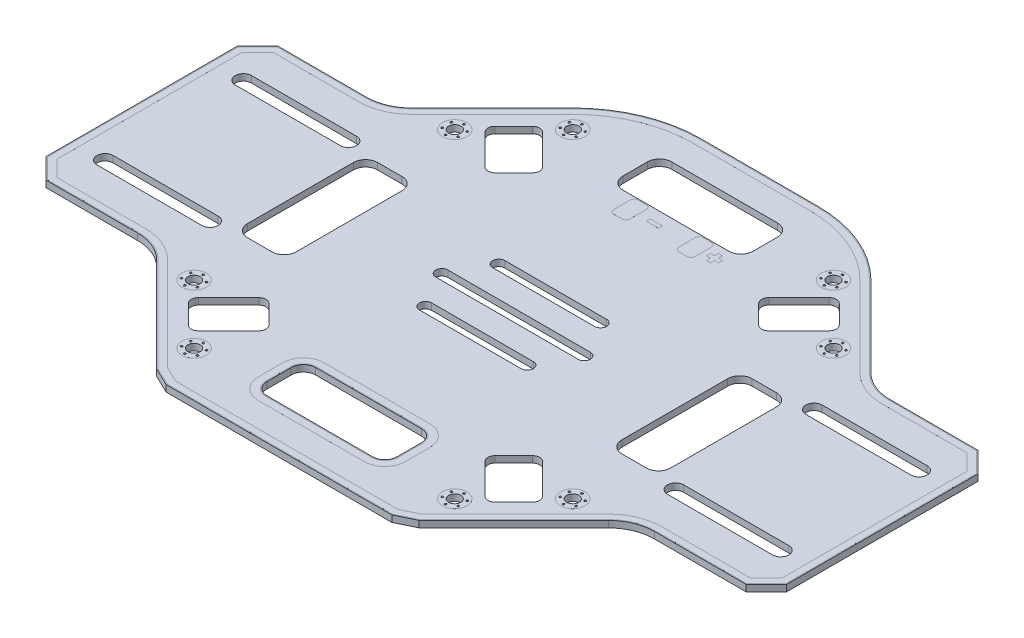
SolidWorks part; units mm, degrees
material "PLA"
ref_plane "Front Plane" through (0, 0, 0) normal (0, 0, 1) x (1, 0, 0)
ref_plane "Top Plane" through (0, 0, 0) normal (0, 1, 0) x (1, 0, 0)
ref_plane "Right Plane" through (0, 0, 0) normal (1, 0, 0) x (0, 0, -1)
sketch "Sketch1" plane through (0, 0, 0) normal (0, 1, 0) x (1, 0, 0)
  line L0 (0, 60.3186) -> (0, -57.6814) construction
  line L1 (-27.75, -57.6814) -> (27.75, -57.6814)
  line L2 (-13, -47.6814) -> (13, -47.6814)
  line L3 (-16, -38.6814) -> (-16, -44.6814)
  line L4 (16, -38.6814) -> (16, -44.6814)
  line L5 (-16, -41.6814) -> (16, -41.6814) construction
  line L6 (-13, -35.6814) -> (13, -35.6814)
  line L7 (-27.75, -57.6814) -> (-32.25, -55.502)
  line L8 (27.75, -57.6814) -> (32.25, -55.502)
  line L9 (-32.25, -55.502) -> (32.25, -55.502) construction
  line L10 (32.25, -55.502) -> (55.502, -32.25)
  line L11 (-32.25, -55.502) -> (-55.502, -32.25)
  line L12 (-43.876, 43.876) -> (43.876, -43.876) construction
  line L13 (-43.876, -43.876) -> (43.876, 43.876) construction
  line L14 (37.6888, -42.285) -> (42.285, -37.6888)
  line L15 (27.7893, -34.8604) -> (35.2139, -42.285)
  line L16 (34.8604, -27.7893) -> (42.285, -35.2139)
  line L17 (31.5016, -38.5727) -> (38.5727, -31.5016) construction
  line L18 (27.7893, -32.3855) -> (32.3855, -27.7893)
  line L19 (-38.5727, -31.5016) -> (-31.5016, -38.5727) construction
  line L20 (-35.2139, -42.285) -> (-27.7893, -34.8604)
  line L21 (-42.285, -35.2139) -> (-34.8604, -27.7893)
  line L22 (-32.3855, -27.7893) -> (-27.7893, -32.3855)
  line L23 (-42.285, -37.6888) -> (-37.6888, -42.285)
  line L24 (-63.5, -28.9371) -> (63.5, -28.9371) construction
  line L25 (63.5, -28.9371) -> (86, -28.9371)
  line L26 (-63.5, -28.9371) -> (-86, -28.9371)
  line L27 (-91, -23.9371) -> (-91, 23.0629)
  line L28 (91, -23.9371) -> (91, 23.0629)
  line L29 (-86, -28.9371) -> (-86, 28.0629) construction
  line L30 (86, -28.9371) -> (86, 28.0629) construction
  line L31 (-91, -0.4371) -> (-86, -0.4371) construction
  line L32 (86, -0.4371) -> (91, -0.4371) construction
  line L33 (86, -28.9371) -> (91, -23.9371)
  line L34 (-91, -23.9371) -> (-86, -28.9371)
  line L35 (91, 23.0629) -> (86, 28.0629)
  line L36 (-91, 23.0629) -> (-86, 28.0629)
  line L37 (-56.4271, 31.3248) -> (-36.6281, 51.1238)
  line L38 (36.6281, 51.1238) -> (56.4271, 31.3248)
  line L39 (-35.2139, 42.285) -> (-27.7893, 34.8604)
  line L40 (-36.6281, 51.1238) -> (-27.7893, 42.285) construction
  line L41 (-27.7893, 42.285) -> (-31.5016, 38.5727) construction
  line L42 (-42.285, 35.2139) -> (-34.8604, 27.7893)
  line L43 (-31.5016, 38.5727) -> (-38.5727, 31.5016) construction
  line L44 (-42.285, 37.6888) -> (-37.6888, 42.285)
  line L45 (-32.3855, 27.7893) -> (-27.7893, 32.3855)
  line L46 (-86, 28.0629) -> (-64.3021, 28.0629)
  line L47 (86, 28.0629) -> (64.3021, 28.0629)
  line L48 (37.6888, 42.285) -> (42.285, 37.6888)
  line L49 (27.7893, 32.3855) -> (32.3855, 27.7893)
  line L50 (27.7893, 34.8604) -> (35.2139, 42.285)
  line L51 (34.8604, 27.7893) -> (42.285, 35.2139)
  line L52 (31.5016, 38.5727) -> (38.5727, 31.5016) construction
  line L53 (31.5016, 38.5727) -> (27.7893, 42.285) construction
  line L54 (27.7893, 42.285) -> (36.6281, 51.1238) construction
  line L55 (-14.43, 60.3186) -> (14.43, 60.3186)
  line L56 (-13, 51.8186) -> (13, 51.8186)
  line L57 (-13, 39.8186) -> (13, 39.8186)
  line L58 (16, 48.8186) -> (16, 42.8186)
  line L59 (-16, 48.8186) -> (-16, 42.8186)
  line L60 (-12.5, -10.6814) -> (12.5, -10.6814)
  line L61 (-12.5, -7.6814) -> (12.5, -7.6814)
  line L62 (-17.5, -1.6814) -> (17.5, -1.6814)
  line L63 (-17.5, 1.3186) -> (17.5, 1.3186)
  line L64 (-12.5, 7.3186) -> (12.5, 7.3186)
  line L65 (-12.5, 10.3186) -> (12.5, 10.3186)
  line L66 (-52, 12.5629) -> (-52, -13.4371)
  line L67 (-86, -0.4371) -> (-52, -0.4371) construction
  line L68 (-40, 12.5629) -> (-40, -13.4371)
  line L69 (52, 12.5629) -> (52, -13.4371)
  line L70 (-49, 15.5629) -> (-43, 15.5629)
  line L71 (-49, -16.4371) -> (-43, -16.4371)
  line L72 (86, -0.4371) -> (52, -0.4371) construction
  line L73 (40, 12.5629) -> (40, -13.4371)
  line L74 (43, 15.5629) -> (49, 15.5629)
  line L75 (43, -16.4371) -> (49, -16.4371)
  line L76 (-83, 18.5629) -> (-57.2, 18.5629)
  line L77 (-83, 14.5629) -> (-57.2, 14.5629)
  line L78 (-83, -15.4371) -> (-57.2, -15.4371)
  line L79 (-83, -19.4371) -> (-57.2, -19.4371)
  line L80 (57.2, -15.4371) -> (83, -15.4371)
  line L81 (57.2, -19.4371) -> (83, -19.4371)
  line L82 (57.2, 18.5629) -> (83, 18.5629)
  line L83 (57.2, 14.5629) -> (83, 14.5629)
  line L84 (-46.5276, 32.0319) -> (-32.0319, 46.5276) construction
  line L85 (32.0319, -46.5276) -> (46.5276, -32.0319) construction
  arc A0 (-16, -44.6814) -> (-13, -47.6814) centre (-13, -44.6814) ccw
  arc A1 (-13, -35.6814) -> (-16, -38.6814) centre (-13, -38.6814) ccw
  arc A2 (16, -38.6814) -> (13, -35.6814) centre (13, -38.6814) ccw
  arc A3 (13, -47.6814) -> (16, -44.6814) centre (13, -44.6814) ccw
  arc A4 (27.7893, -32.3855) -> (27.7893, -34.8604) centre (29.0267, -33.6229) ccw
  arc A5 (34.8604, -27.7893) -> (32.3855, -27.7893) centre (33.6229, -29.0267) ccw
  arc A6 (35.2139, -42.285) -> (37.6888, -42.285) centre (36.4514, -41.0475) ccw
  arc A7 (42.285, -37.6888) -> (42.285, -35.2139) centre (41.0475, -36.4514) ccw
  arc A8 (-37.6888, -42.285) -> (-35.2139, -42.285) centre (-36.4514, -41.0475) ccw
  arc A9 (-42.285, -35.2139) -> (-42.285, -37.6888) centre (-41.0475, -36.4514) ccw
  arc A10 (-32.3855, -27.7893) -> (-34.8604, -27.7893) centre (-33.6229, -29.0267) ccw
  arc A11 (-27.7893, -34.8604) -> (-27.7893, -32.3855) centre (-29.0267, -33.6229) ccw
  arc A12 (-55.502, -32.25) -> (-63.5, -28.9371) centre (-63.5, -40.248) ccw
  arc A13 (63.5, -28.9371) -> (55.502, -32.25) centre (63.5, -40.248) ccw
  arc A14 (-42.285, 37.6888) -> (-42.285, 35.2139) centre (-41.0475, 36.4514) ccw
  arc A15 (-35.2139, 42.285) -> (-37.6888, 42.285) centre (-36.4514, 41.0475) ccw
  arc A16 (-27.7893, 32.3855) -> (-27.7893, 34.8604) centre (-29.0267, 33.6229) ccw
  arc A17 (-34.8604, 27.7893) -> (-32.3855, 27.7893) centre (-33.6229, 29.0267) ccw
  arc A18 (-64.3021, 28.0629) -> (-56.4271, 31.3248) centre (-64.3021, 39.1998) ccw
  arc A19 (56.4271, 31.3248) -> (64.3021, 28.0629) centre (64.3021, 39.1998) ccw
  arc A20 (27.7893, 34.8604) -> (27.7893, 32.3855) centre (29.0267, 33.6229) ccw
  arc A21 (37.6888, 42.285) -> (35.2139, 42.285) centre (36.4514, 41.0475) ccw
  arc A22 (42.285, 35.2139) -> (42.285, 37.6888) centre (41.0475, 36.4514) ccw
  arc A23 (32.3855, 27.7893) -> (34.8604, 27.7893) centre (33.6229, 29.0267) ccw
  arc A24 (-14.43, 60.3186) -> (-36.6281, 51.1238) centre (-14.43, 28.9257) ccw
  arc A25 (13, 39.8186) -> (16, 42.8186) centre (13, 42.8186) ccw
  arc A26 (36.6281, 51.1238) -> (14.43, 60.3186) centre (14.43, 28.9257) ccw
  arc A27 (16, 48.8186) -> (13, 51.8186) centre (13, 48.8186) ccw
  arc A28 (-16, 42.8186) -> (-13, 39.8186) centre (-13, 42.8186) ccw
  arc A29 (-13, 51.8186) -> (-16, 48.8186) centre (-13, 48.8186) ccw
  arc A30 (-12.5, -7.6814) -> (-12.5, -10.6814) centre (-12.5, -9.1814) ccw
  arc A31 (12.5, -10.6814) -> (12.5, -7.6814) centre (12.5, -9.1814) ccw
  arc A32 (-17.5, 1.3186) -> (-17.5, -1.6814) centre (-17.5, -0.1814) ccw
  arc A33 (17.5, -1.6814) -> (17.5, 1.3186) centre (17.5, -0.1814) ccw
  arc A34 (-12.5, 10.3186) -> (-12.5, 7.3186) centre (-12.5, 8.8186) ccw
  arc A35 (12.5, 7.3186) -> (12.5, 10.3186) centre (12.5, 8.8186) ccw
  arc A36 (-49, 15.5629) -> (-52, 12.5629) centre (-49, 12.5629) ccw
  arc A37 (-40, 12.5629) -> (-43, 15.5629) centre (-43, 12.5629) ccw
  arc A38 (-52, -13.4371) -> (-49, -16.4371) centre (-49, -13.4371) ccw
  arc A39 (-43, -16.4371) -> (-40, -13.4371) centre (-43, -13.4371) ccw
  arc A40 (43, 15.5629) -> (40, 12.5629) centre (43, 12.5629) ccw
  arc A41 (52, 12.5629) -> (49, 15.5629) centre (49, 12.5629) ccw
  arc A42 (40, -13.4371) -> (43, -16.4371) centre (43, -13.4371) ccw
  arc A43 (49, -16.4371) -> (52, -13.4371) centre (49, -13.4371) ccw
  arc A44 (-57.2, 14.5629) -> (-57.2, 18.5629) centre (-57.2, 16.5629) ccw
  arc A45 (-83, 18.5629) -> (-83, 14.5629) centre (-83, 16.5629) ccw
  arc A46 (-83, -15.4371) -> (-83, -19.4371) centre (-83, -17.4371) ccw
  arc A47 (-57.2, -19.4371) -> (-57.2, -15.4371) centre (-57.2, -17.4371) ccw
  arc A48 (57.2, -15.4371) -> (57.2, -19.4371) centre (57.2, -17.4371) ccw
  arc A49 (83, -19.4371) -> (83, -15.4371) centre (83, -17.4371) ccw
  arc A50 (57.2, 18.5629) -> (57.2, 14.5629) centre (57.2, 16.5629) ccw
  arc A51 (83, 14.5629) -> (83, 18.5629) centre (83, 16.5629) ccw
  circle A52 centre (-32.0319, 46.5276) radius 1.5
  circle A53 centre (-46.5276, 32.0319) radius 1.5
  circle A54 centre (32.0319, -46.5276) radius 1.5
  circle A55 centre (46.5276, -32.0319) radius 1.5
  circle A56 centre (-46.5276, -32.0319) radius 1.5
  circle A57 centre (-32.0319, -46.5276) radius 1.5
  circle A58 centre (32.0319, 46.5276) radius 1.5
  circle A59 centre (46.5276, 32.0319) radius 1.5
  point P4 (-35.0371, 35.0371)
  point P5 (0, -47.6814)
  point P14 (0, -41.6814)
  point P15 (0, -35.6814)
  point P19 (0, -55.502)
  point P29 (0, 0)
  point P30 (39.9869, -39.9869)
  point P32 (0, 0)
  point P42 (30.0874, -30.0874)
  point P43 (35.0371, -35.0371)
  point P50 (-35.0371, -35.0371)
  point P53 (-38.5727, -31.5016)
  point P62 (-39.9869, -39.9869)
  point P63 (-30.0874, -30.0874)
  point P70 (0, -28.9371)
  point P99 (-39.9869, 39.9869)
  point P102 (-30.0874, 30.0874)
  point P119 (35.0371, 35.0371)
  point P122 (39.9869, 39.9869)
  point P123 (30.0874, 30.0874)
  point P135 (0, 51.8186)
  point P138 (0, 39.8186)
  point P147 (0, -10.6814)
  point P151 (-14, -9.1814)
  point P153 (14, -9.1814)
  point P156 (0, -1.6814)
  point P158 (-19, -0.1814)
  point P162 (19, -0.1814)
  point P167 (0, 7.3186)
  point P203 (-85, 16.5629)
  point P205 (-55.2, 16.5629)
  point P217 (85, -17.4371)
  point P229 (-39.2798, 39.2798)
  point P232 (39.2798, -39.2798)
  dimension "D5" = 12
  dimension "D6" = 55.5
  dimension "D14" = 14
  dimension "D15" = 127
  dimension "D16" = 22.5
  dimension "D23" = 8.5
  dimension "D24" = 25
  dimension "D25" = 3
  dimension "D28" = 3
  dimension "D31" = 39
  dimension "D32" = 9.5
  dimension "D34" = 29.8
  dimension "D38" = 6
  dimension "D39" = 3
  dimension "D1" = 118
  dimension "D2" = 10
  dimension "D3" = 32
  dimension "D4" = 6
  dimension "D7" = 64.5
  dimension "D8" = 5
  dimension "D9" = 124.1
  dimension "D10" = 45
  dimension "D11" = 5.5
  dimension "D12" = 6.5
  dimension "D13" = 10
  dimension "D17" = 22.5
  dimension "D18" = 5
  dimension "D19" = 45
  dimension "D20" = 47
  dimension "D21" = 28
  dimension "D22" = 5.25
  dimension "D26" = 28
  dimension "D27" = 6
  dimension "D29" = 38
  dimension "D30" = 6
  dimension "D33" = 4
  dimension "D35" = 6
  dimension "D36" = 9.5
  dimension "D37" = 4
  dimension "D40" = 6.5
  dimension "D41" = 6.5
extrude "Boss-Extrude1" add sketch "Sketch1" along normal blind 0.8 and the other way blind 0.8
sketch "Sketch2" plane through (0, 0.8, 0) normal (0, 1, 0) x (1, 0, 0)
  line L0 (-27.6926, -57.4314) -> (27.6926, -57.4314)
  line L1 (-27.75, -57.6814) -> (27.75, -57.6814) construction
  line L2 (-27.6926, -57.4314) -> (-32.1031, -55.2953)
  line L3 (-32.25, -55.502) -> (-27.75, -57.6814) construction
  line L4 (27.6926, -57.4314) -> (32.1031, -55.2953)
  line L5 (27.75, -57.6814) -> (32.25, -55.502) construction
  line L6 (0, -57.6814) -> (0, -57.4314) construction
  line L7 (-32.1031, -55.2953) -> (-55.3252, -32.0732)
  line L8 (-55.502, -32.25) -> (-32.25, -55.502) construction
  line L9 (32.1031, -55.2953) -> (55.3252, -32.0732)
  line L10 (32.25, -55.502) -> (55.502, -32.25) construction
  line L11 (-85.8964, -28.6871) -> (-63.5, -28.6871)
  line L12 (-85.8964, -28.6871) -> (-90.75, -23.8335)
  line L13 (-91, -23.9371) -> (-86, -28.9371) construction
  line L14 (-86, -28.9371) -> (-63.5, -28.9371) construction
  line L15 (63.5, -28.6871) -> (85.8964, -28.6871)
  line L16 (85.8964, -28.6871) -> (90.75, -23.8335)
  line L17 (-90.75, -23.8335) -> (-90.75, 22.9593)
  line L18 (-91, 23.0629) -> (-91, -23.9371) construction
  line L19 (-90.75, 22.9593) -> (-85.8964, 27.8129)
  line L20 (-85.8964, 27.8129) -> (-64.3021, 27.8129)
  line L21 (-64.3021, 28.0629) -> (-86, 28.0629) construction
  line L22 (-56.2503, 31.1481) -> (-36.4514, 50.947)
  line L23 (-36.6281, 51.1238) -> (-56.4271, 31.3248) construction
  line L24 (-14.43, 60.0686) -> (14.43, 60.0686)
  line L25 (14.43, 60.3186) -> (-14.43, 60.3186) construction
  line L26 (56.2503, 31.1481) -> (36.4514, 50.947)
  line L27 (56.4271, 31.3248) -> (36.6281, 51.1238) construction
  line L28 (64.3021, 27.8129) -> (85.8964, 27.8129)
  line L29 (86, 28.0629) -> (64.3021, 28.0629) construction
  line L30 (85.8964, 27.8129) -> (90.75, 22.9593)
  line L31 (91, 23.0629) -> (86, 28.0629) construction
  line L32 (90.75, 22.9593) -> (90.75, -23.8335)
  line L33 (-55.0836, 29.9813) -> (-35.2846, 49.7803)
  line L34 (-14.43, 58.4186) -> (14.43, 58.4186)
  line L35 (55.0836, 29.9813) -> (35.2846, 49.7803)
  line L36 (64.3021, 26.1629) -> (85.213, 26.1629)
  line L37 (85.213, 26.1629) -> (89.1, 22.2759)
  line L38 (89.1, 22.2759) -> (89.1, -23.1501)
  line L39 (85.213, -27.0371) -> (89.1, -23.1501)
  line L40 (63.5, -27.0371) -> (85.213, -27.0371)
  line L41 (31.1332, -53.9317) -> (54.1584, -30.9065)
  line L42 (27.3141, -55.7814) -> (31.1332, -53.9317)
  line L43 (-27.3141, -55.7814) -> (27.3141, -55.7814)
  line L44 (-27.3141, -55.7814) -> (-31.1332, -53.9317)
  line L45 (-31.1332, -53.9317) -> (-54.1584, -30.9065)
  line L46 (-85.213, -27.0371) -> (-63.5, -27.0371)
  line L47 (-85.213, -27.0371) -> (-89.1, -23.1501)
  line L48 (-89.1, -23.1501) -> (-89.1, 22.2759)
  line L49 (-89.1, 22.2759) -> (-85.213, 26.1629)
  line L50 (-85.213, 26.1629) -> (-64.3021, 26.1629)
  line L51 (-13, -35.4314) -> (13, -35.4314)
  line L52 (-16.25, -38.6814) -> (-16.25, -44.6814)
  line L53 (-13, -47.9314) -> (13, -47.9314)
  line L54 (16.25, -44.6814) -> (16.25, -38.6814)
  line L55 (16, -44.6814) -> (16, -38.6814) construction
  line L56 (13, -35.6814) -> (-13, -35.6814) construction
  line L57 (-16, -38.6814) -> (-16, -44.6814) construction
  line L58 (-13, -47.6814) -> (13, -47.6814) construction
  line L59 (-13, -33.6314) -> (13, -33.6314)
  line L60 (18.05, -44.6814) -> (18.05, -38.6814)
  line L61 (-13, -49.7314) -> (13, -49.7314)
  line L62 (-18.05, -38.6814) -> (-18.05, -44.6814)
  line L63 (32.0319, -43.5276) -> (32.0319, -44.2776) construction
  line L64 (-32.0319, -44.2776) -> (-33.9805, -45.4026) construction
  line L65 (-33.9805, -45.4026) -> (-33.9805, -47.6526) construction
  line L66 (-33.9805, -47.6526) -> (-32.0319, -48.7776) construction
  line L67 (-32.0319, -48.7776) -> (-30.0834, -47.6526) construction
  line L68 (-30.0834, -47.6526) -> (-30.0834, -45.4026) construction
  line L69 (-30.0834, -45.4026) -> (-32.0319, -44.2776) construction
  line L70 (-46.5276, -29.7819) -> (-48.4762, -30.9069) construction
  line L71 (-48.4762, -30.9069) -> (-48.4762, -33.1569) construction
  line L72 (-48.4762, -33.1569) -> (-46.5276, -34.2819) construction
  line L73 (-46.5276, -34.2819) -> (-44.5791, -33.1569) construction
  line L74 (-44.5791, -33.1569) -> (-44.5791, -30.9069) construction
  line L75 (-44.5791, -30.9069) -> (-46.5276, -29.7819) construction
  line L76 (-46.5276, 34.2819) -> (-48.4762, 33.1569) construction
  line L77 (-48.4762, 33.1569) -> (-48.4762, 30.9069) construction
  line L78 (-48.4762, 30.9069) -> (-46.5276, 29.7819) construction
  line L79 (-46.5276, 29.7819) -> (-44.5791, 30.9069) construction
  line L80 (-44.5791, 30.9069) -> (-44.5791, 33.1569) construction
  line L81 (-44.5791, 33.1569) -> (-46.5276, 34.2819) construction
  line L82 (-32.0319, 48.7776) -> (-33.9805, 47.6526) construction
  line L83 (-33.9805, 47.6526) -> (-33.9805, 45.4026) construction
  line L84 (-33.9805, 45.4026) -> (-32.0319, 44.2776) construction
  line L85 (-32.0319, 44.2776) -> (-30.0834, 45.4026) construction
  line L86 (-30.0834, 45.4026) -> (-30.0834, 47.6526) construction
  line L87 (-30.0834, 47.6526) -> (-32.0319, 48.7776) construction
  line L88 (32.0319, 48.7776) -> (30.0834, 47.6526) construction
  line L89 (30.0834, 47.6526) -> (30.0834, 45.4026) construction
  line L90 (30.0834, 45.4026) -> (32.0319, 44.2776) construction
  line L91 (32.0319, 44.2776) -> (33.9805, 45.4026) construction
  line L92 (33.9805, 45.4026) -> (33.9805, 47.6526) construction
  line L93 (33.9805, 47.6526) -> (32.0319, 48.7776) construction
  line L94 (46.5276, 34.2819) -> (44.5791, 33.1569) construction
  line L95 (44.5791, 33.1569) -> (44.5791, 30.9069) construction
  line L96 (44.5791, 30.9069) -> (46.5276, 29.7819) construction
  line L97 (46.5276, 29.7819) -> (48.4762, 30.9069) construction
  line L98 (48.4762, 30.9069) -> (48.4762, 33.1569) construction
  line L99 (48.4762, 33.1569) -> (46.5276, 34.2819) construction
  line L100 (46.5276, -29.7819) -> (44.5791, -30.9069) construction
  line L101 (44.5791, -30.9069) -> (44.5791, -33.1569) construction
  line L102 (44.5791, -33.1569) -> (46.5276, -34.2819) construction
  line L103 (46.5276, -34.2819) -> (48.4762, -33.1569) construction
  line L104 (48.4762, -33.1569) -> (48.4762, -30.9069) construction
  line L105 (48.4762, -30.9069) -> (46.5276, -29.7819) construction
  line L106 (32.0319, -44.2776) -> (30.0834, -45.4026) construction
  line L107 (30.0834, -45.4026) -> (30.0834, -47.6526) construction
  line L108 (30.0834, -47.6526) -> (32.0319, -48.7776) construction
  line L109 (32.0319, -48.7776) -> (33.9805, -47.6526) construction
  line L110 (33.9805, -47.6526) -> (33.9805, -45.4026) construction
  line L111 (33.9805, -45.4026) -> (32.0319, -44.2776) construction
  line L112 (32.0319, -44.2776) -> (32.0319, -45.0276) construction
  arc A0 (-55.3252, -32.0732) -> (-63.5, -28.6871) centre (-63.5, -40.248) ccw
  arc A1 (-55.502, -32.25) -> (-63.5, -28.9371) centre (-63.5, -40.248) ccw construction
  arc A2 (63.5, -28.6871) -> (55.3252, -32.0732) centre (63.5, -40.248) ccw
  arc A3 (63.5, -28.9371) -> (55.502, -32.25) centre (63.5, -40.248) ccw construction
  arc A4 (-64.3021, 27.8129) -> (-56.2503, 31.1481) centre (-64.3021, 39.1998) ccw
  arc A5 (-64.3021, 28.0629) -> (-56.4271, 31.3248) centre (-64.3021, 39.1998) ccw construction
  arc A6 (-14.43, 60.0686) -> (-36.4514, 50.947) centre (-14.43, 28.9257) ccw
  arc A7 (-14.43, 60.3186) -> (-36.6281, 51.1238) centre (-14.43, 28.9257) ccw construction
  arc A8 (36.4514, 50.947) -> (14.43, 60.0686) centre (14.43, 28.9257) ccw
  arc A9 (36.6281, 51.1238) -> (14.43, 60.3186) centre (14.43, 28.9257) ccw construction
  arc A10 (56.2503, 31.1481) -> (64.3021, 27.8129) centre (64.3021, 39.1998) ccw
  arc A11 (56.4271, 31.3248) -> (64.3021, 28.0629) centre (64.3021, 39.1998) ccw construction
  arc A12 (-14.43, 58.4186) -> (-35.2846, 49.7803) centre (-14.43, 28.9257) ccw
  arc A13 (35.2846, 49.7803) -> (14.43, 58.4186) centre (14.43, 28.9257) ccw
  arc A14 (55.0836, 29.9813) -> (64.3021, 26.1629) centre (64.3021, 39.1998) ccw
  arc A15 (63.5, -27.0371) -> (54.1584, -30.9065) centre (63.5, -40.248) ccw
  arc A16 (-54.1584, -30.9065) -> (-63.5, -27.0371) centre (-63.5, -40.248) ccw
  arc A17 (-64.3021, 26.1629) -> (-55.0836, 29.9813) centre (-64.3021, 39.1998) ccw
  arc A18 (-13, -35.4314) -> (-16.25, -38.6814) centre (-13, -38.6814) ccw
  arc A19 (16.25, -38.6814) -> (13, -35.4314) centre (13, -38.6814) ccw
  arc A20 (-16.25, -44.6814) -> (-13, -47.9314) centre (-13, -44.6814) ccw
  arc A21 (13, -47.9314) -> (16.25, -44.6814) centre (13, -44.6814) ccw
  arc A22 (-13, -35.6814) -> (-16, -38.6814) centre (-13, -38.6814) ccw construction
  arc A23 (-16, -44.6814) -> (-13, -47.6814) centre (-13, -44.6814) ccw construction
  arc A24 (16, -38.6814) -> (13, -35.6814) centre (13, -38.6814) ccw construction
  arc A25 (13, -47.6814) -> (16, -44.6814) centre (13, -44.6814) ccw construction
  arc A26 (18.05, -38.6814) -> (13, -33.6314) centre (13, -38.6814) ccw
  arc A27 (13, -49.7314) -> (18.05, -44.6814) centre (13, -44.6814) ccw
  arc A28 (-18.05, -44.6814) -> (-13, -49.7314) centre (-13, -44.6814) ccw
  arc A29 (-13, -33.6314) -> (-18.05, -38.6814) centre (-13, -38.6814) ccw
  circle A30 centre (-32.0319, -46.5276) radius 1.5
  circle A31 centre (-46.5276, -32.0319) radius 1.5
  circle A32 centre (-46.5276, 32.0319) radius 1.5
  circle A33 centre (-32.0319, 46.5276) radius 1.5
  circle A34 centre (32.0319, 46.5276) radius 1.5
  circle A35 centre (46.5276, 32.0319) radius 1.5
  circle A36 centre (46.5276, -32.0319) radius 1.5
  circle A37 centre (32.0319, -46.5276) radius 1.5
  circle A38 centre (-32.0319, -46.5276) radius 1.5 construction
  circle A39 centre (-46.5276, -32.0319) radius 1.5 construction
  circle A40 centre (-46.5276, 32.0319) radius 1.5 construction
  circle A41 centre (-32.0319, 46.5276) radius 1.5 construction
  circle A42 centre (32.0319, 46.5276) radius 1.5 construction
  circle A43 centre (46.5276, 32.0319) radius 1.5 construction
  circle A44 centre (46.5276, -32.0319) radius 1.5 construction
  circle A45 centre (32.0319, -46.5276) radius 1.5 construction
  circle A46 centre (-32.0319, -46.5276) radius 3
  circle A47 centre (-46.5276, -32.0319) radius 3
  circle A48 centre (-46.5276, 32.0319) radius 3
  circle A49 centre (-32.0319, 46.5276) radius 3
  circle A50 centre (32.0319, 46.5276) radius 3
  circle A51 centre (46.5276, 32.0319) radius 3
  circle A52 centre (46.5276, -32.0319) radius 3
  circle A53 centre (32.0319, -46.5276) radius 3
  circle A54 centre (-32.0319, -46.5276) radius 1.9486 construction
  circle A55 centre (-46.5276, -32.0319) radius 1.9486 construction
  circle A56 centre (-46.5276, 32.0319) radius 1.9486 construction
  circle A57 centre (-32.0319, 46.5276) radius 1.9486 construction
  circle A58 centre (32.0319, 46.5276) radius 1.9486 construction
  circle A59 centre (46.5276, 32.0319) radius 1.9486 construction
  circle A60 centre (46.5276, -32.0319) radius 1.9486 construction
  circle A61 centre (32.0319, -46.5276) radius 1.9486 construction
  circle A62 centre (32.0319, -44.2776) radius 0.25
  circle A63 centre (33.9805, -45.4026) radius 0.25
  circle A64 centre (33.9805, -47.6526) radius 0.25
  circle A65 centre (32.0319, -48.7776) radius 0.25
  circle A66 centre (30.0834, -47.6526) radius 0.25
  circle A67 centre (30.0834, -45.4026) radius 0.25
  circle A68 centre (46.5276, -34.2819) radius 0.25
  circle A69 centre (48.4762, -33.1569) radius 0.25
  circle A70 centre (48.4762, -30.9069) radius 0.25
  circle A71 centre (46.5276, -29.7819) radius 0.25
  circle A72 centre (44.5791, -30.9069) radius 0.25
  circle A73 centre (44.5791, -33.1569) radius 0.25
  circle A74 centre (46.5276, 29.7819) radius 0.25
  circle A75 centre (48.4762, 30.9069) radius 0.25
  circle A76 centre (48.4762, 33.1569) radius 0.25
  circle A77 centre (46.5276, 34.2819) radius 0.25
  circle A78 centre (44.5791, 33.1569) radius 0.25
  circle A79 centre (44.5791, 30.9069) radius 0.25
  circle A80 centre (32.0319, 44.2776) radius 0.25
  circle A81 centre (33.9805, 45.4026) radius 0.25
  circle A82 centre (33.9805, 47.6526) radius 0.25
  circle A83 centre (32.0319, 48.7776) radius 0.25
  circle A84 centre (30.0834, 47.6526) radius 0.25
  circle A85 centre (30.0834, 45.4026) radius 0.25
  circle A86 centre (-32.0319, 48.7776) radius 0.25
  circle A87 centre (-30.0834, 47.6526) radius 0.25
  circle A88 centre (-30.0834, 45.4026) radius 0.25
  circle A89 centre (-32.0319, 44.2776) radius 0.25
  circle A90 centre (-33.9805, 47.6526) radius 0.25
  circle A91 centre (-33.9805, 45.4026) radius 0.25
  circle A92 centre (-46.5276, 29.7819) radius 0.25
  circle A93 centre (-44.5791, 30.9069) radius 0.25
  circle A94 centre (-44.5791, 33.1569) radius 0.25
  circle A95 centre (-46.5276, 34.2819) radius 0.25
  circle A96 centre (-48.4762, 33.1569) radius 0.25
  circle A97 centre (-48.4762, 30.9069) radius 0.25
  circle A98 centre (-46.5276, -29.7819) radius 0.25
  circle A99 centre (-44.5791, -30.9069) radius 0.25
  circle A100 centre (-44.5791, -33.1569) radius 0.25
  circle A101 centre (-46.5276, -34.2819) radius 0.25
  circle A102 centre (-48.4762, -33.1569) radius 0.25
  circle A103 centre (-48.4762, -30.9069) radius 0.25
  circle A104 centre (-32.0319, -44.2776) radius 0.25
  circle A105 centre (-30.0834, -45.4026) radius 0.25
  circle A106 centre (-30.0834, -47.6526) radius 0.25
  circle A107 centre (-32.0319, -48.7776) radius 0.25
  circle A108 centre (-33.9805, -47.6526) radius 0.25
  circle A109 centre (-33.9805, -45.4026) radius 0.25
  dimension "D2" = 0.25
  dimension "D5" = 0.25
  dimension "D7" = 1.65
  dimension "D8" = 0.25
  dimension "D10" = 6
  dimension "D11" = 0.5
  dimension "D1" = 0.25
  dimension "D3" = 0.25
  dimension "D4" = 0.25
  dimension "D6" = 0.25
  dimension "D9" = 1.8
extrude "Boss-Extrude2" add sketch "Sketch2" along normal blind 0.001 contours A10 L26 A8 L24 A6 L22 A4 L20 L19 L17 L12 L11 A0 L7 L2 L0 L4 L9 A2 L15 L16 L32 L30 L28 L50 A17 L33 A12 L34 A13 L35 A14 L36 L37 L38 L39 L40 A15 L41 L42 L43 L44 L45 A16 L46 L47 L48 L49 | A46 A109 A108 A107 A106 A105 A104 A30 | A47 A103 A102 A101 A100 A99 A98 A31 | A48 A97 A96 A95 A94 A93 A92 A32 | A49 A91 A90 A89 A88 A87 A86 A33 | A50 A85 A84 A83 A82 A81 A80 A34 | A51 A79 A78 A77 A76 A75 A74 A35 | A52 A73 A72 A71 A70 A69 A68 A36 | A53 A67 A66 A65 A64 A63 A62 A37 | L59 A29 L62 A28 L61 A27 L60 A26 A21 L53 A20 L52 A18 L51 A19 L54 region at (-29.8036, 0.8, 56.1688) region at (0, 0.8, 34.0267) region at (-34.9471, 0.8, 46.5276) region at (-49.4428, 0.8, 32.0319) region at (-49.4428, 0.8, -32.0319) region at (-34.9471, 0.8, -46.5276) region at (29.1168, 0.8, -46.5276) region at (43.6125, 0.8, -32.0319) region at (43.6125, 0.8, 32.0319) region at (29.1168, 0.8, 46.5276)
mirror "Mirror1" about plane through (0, 0, 0) normal (0, 1, 0) of "Boss-Extrude2"
sketch "Sketch6" plane through (0, 0.8, 0) normal (0, 1, 0) x (1, 0, 0)
  circle A0 centre (-48.4762, 33.1569) radius 0.25
  circle A1 centre (-46.5276, 34.2819) radius 0.25
  circle A2 centre (-44.5791, 33.1569) radius 0.25
  circle A3 centre (-48.4762, 30.9069) radius 0.25
  circle A4 centre (-46.5276, 29.7819) radius 0.25
  circle A5 centre (-44.5791, 30.9069) radius 0.25
  circle A6 centre (-33.9805, 45.4026) radius 0.25
  circle A7 centre (-32.0319, 48.7776) radius 0.25
  circle A8 centre (-33.9805, 47.6526) radius 0.25
  circle A9 centre (-32.0319, 44.2776) radius 0.25
  circle A10 centre (-30.0834, 47.6526) radius 0.25
  circle A11 centre (-30.0834, 45.4026) radius 0.25
  circle A12 centre (30.0834, 47.6526) radius 0.25
  circle A13 centre (32.0319, 48.7776) radius 0.25
  circle A14 centre (33.9805, 47.6526) radius 0.25
  circle A15 centre (33.9805, 45.4026) radius 0.25
  circle A16 centre (30.0834, 45.4026) radius 0.25
  circle A17 centre (32.0319, 44.2776) radius 0.25
  circle A18 centre (46.5276, 34.2819) radius 0.25
  circle A19 centre (48.4762, 30.9069) radius 0.25
  circle A20 centre (44.5791, 33.1569) radius 0.25
  circle A21 centre (48.4762, 33.1569) radius 0.25
  circle A22 centre (46.5276, 29.7819) radius 0.25
  circle A23 centre (44.5791, 30.9069) radius 0.25
  circle A24 centre (44.5791, -30.9069) radius 0.25
  circle A25 centre (46.5276, -29.7819) radius 0.25
  circle A26 centre (44.5791, -33.1569) radius 0.25
  circle A27 centre (48.4762, -33.1569) radius 0.25
  circle A28 centre (48.4762, -30.9069) radius 0.25
  circle A29 centre (46.5276, -34.2819) radius 0.25
  circle A30 centre (32.0319, -44.2776) radius 0.25
  circle A31 centre (30.0834, -45.4026) radius 0.25
  circle A32 centre (30.0834, -47.6526) radius 0.25
  circle A33 centre (33.9805, -47.6526) radius 0.25
  circle A34 centre (32.0319, -48.7776) radius 0.25
  circle A35 centre (33.9805, -45.4026) radius 0.25
  circle A36 centre (-48.4762, -30.9069) radius 0.25
  circle A37 centre (-44.5791, -30.9069) radius 0.25
  circle A38 centre (-48.4762, -33.1569) radius 0.25
  circle A39 centre (-46.5276, -34.2819) radius 0.25
  circle A40 centre (-44.5791, -33.1569) radius 0.25
  circle A41 centre (-46.5276, -29.7819) radius 0.25
  circle A42 centre (-33.9805, -45.4026) radius 0.25
  circle A43 centre (-32.0319, -44.2776) radius 0.25
  circle A44 centre (-30.0834, -45.4026) radius 0.25
  circle A45 centre (-30.0834, -47.6526) radius 0.25
  circle A46 centre (-33.9805, -47.6526) radius 0.25
  circle A47 centre (-32.0319, -48.7776) radius 0.25
  circle A48 centre (-48.4762, 33.1569) radius 0.25 construction
  circle A49 centre (-46.5276, 34.2819) radius 0.25 construction
  circle A50 centre (-44.5791, 33.1569) radius 0.25 construction
  circle A51 centre (-44.5791, 30.9069) radius 0.25 construction
  circle A52 centre (-46.5276, 29.7819) radius 0.25 construction
  circle A53 centre (-48.4762, 30.9069) radius 0.25 construction
  circle A54 centre (-33.9805, 45.4026) radius 0.25 construction
  circle A55 centre (-33.9805, 47.6526) radius 0.25 construction
  circle A56 centre (-32.0319, 48.7776) radius 0.25 construction
  circle A57 centre (-30.0834, 47.6526) radius 0.25 construction
  circle A58 centre (-30.0834, 45.4026) radius 0.25 construction
  circle A59 centre (-32.0319, 44.2776) radius 0.25 construction
  circle A60 centre (32.0319, 44.2776) radius 0.25 construction
  circle A61 centre (30.0834, 45.4026) radius 0.25 construction
  circle A62 centre (30.0834, 47.6526) radius 0.25 construction
  circle A63 centre (32.0319, 48.7776) radius 0.25 construction
  circle A64 centre (33.9805, 47.6526) radius 0.25 construction
  circle A65 centre (33.9805, 45.4026) radius 0.25 construction
  circle A66 centre (46.5276, 34.2819) radius 0.25 construction
  circle A67 centre (44.5791, 33.1569) radius 0.25 construction
  circle A68 centre (44.5791, 30.9069) radius 0.25 construction
  circle A69 centre (48.4762, 33.1569) radius 0.25 construction
  circle A70 centre (46.5276, 29.7819) radius 0.25 construction
  circle A71 centre (48.4762, 30.9069) radius 0.25 construction
  circle A72 centre (44.5791, -30.9069) radius 0.25 construction
  circle A73 centre (46.5276, -29.7819) radius 0.25 construction
  circle A74 centre (48.4762, -30.9069) radius 0.25 construction
  circle A75 centre (48.4762, -33.1569) radius 0.25 construction
  circle A76 centre (44.5791, -33.1569) radius 0.25 construction
  circle A77 centre (46.5276, -34.2819) radius 0.25 construction
  circle A78 centre (32.0319, -44.2776) radius 0.25 construction
  circle A79 centre (30.0834, -45.4026) radius 0.25 construction
  circle A80 centre (33.9805, -45.4026) radius 0.25 construction
  circle A81 centre (30.0834, -47.6526) radius 0.25 construction
  circle A82 centre (33.9805, -47.6526) radius 0.25 construction
  circle A83 centre (32.0319, -48.7776) radius 0.25 construction
  circle A84 centre (-32.0319, -48.7776) radius 0.25 construction
  circle A85 centre (-33.9805, -47.6526) radius 0.25 construction
  circle A86 centre (-33.9805, -45.4026) radius 0.25 construction
  circle A87 centre (-32.0319, -44.2776) radius 0.25 construction
  circle A88 centre (-30.0834, -45.4026) radius 0.25 construction
  circle A89 centre (-30.0834, -47.6526) radius 0.25 construction
  circle A90 centre (-46.5276, -34.2819) radius 0.25 construction
  circle A91 centre (-48.4762, -33.1569) radius 0.25 construction
  circle A92 centre (-48.4762, -30.9069) radius 0.25 construction
  circle A93 centre (-46.5276, -29.7819) radius 0.25 construction
  circle A94 centre (-44.5791, -30.9069) radius 0.25 construction
  circle A95 centre (-44.5791, -33.1569) radius 0.25 construction
extrude "Cut-Extrude2" cut sketch "Sketch6" against normal up to surface (1.6 mm away) up to face at (35.0371, -0.8, 35.0371)
sketch "Sketch7" plane through (0, 0.8, 0) normal (0, 1, 0) x (1, 0, 0)
  line L0 (9, 39.5686) -> (7, 39.5686)
  line L1 (-7, 39.5686) -> (-9, 39.5686)
  line L2 (8, 39.5686) -> (-8, 39.5686) construction
  line L3 (0, 39.5686) -> (0, 39.8186) construction
  line L4 (-13, 39.8186) -> (13, 39.8186) construction
  line L5 (10, 38.5686) -> (10, 34.5686)
  line L6 (6, 34.5686) -> (6, 38.5686)
  line L7 (9, 33.5686) -> (7, 33.5686)
  line L8 (8, 39.5686) -> (8, 33.5686) construction
  line L9 (10, 36.5686) -> (6, 36.5686) construction
  line L10 (-6, 38.5686) -> (-6, 34.5686)
  line L11 (-7, 33.5686) -> (-9, 33.5686)
  line L12 (-10, 34.5686) -> (-10, 38.5686)
  line L13 (-8, 39.5686) -> (-8, 33.5686) construction
  line L14 (-6, 36.5686) -> (-10, 36.5686) construction
  line L15 (-3.5, 36.0686) -> (-3.5, 37.0686)
  line L16 (-3.5, 37.0686) -> (-0.5, 37.0686)
  line L17 (-0.5, 37.0686) -> (-0.5, 36.0686)
  line L18 (-0.5, 36.0686) -> (-3.5, 36.0686)
  line L19 (-0.5, 36.5686) -> (-3.5, 36.5686) construction
  line L20 (14.25, 36.0686) -> (13.25, 36.0686)
  line L21 (11.25, 36.0686) -> (11.25, 37.0686)
  line L22 (11.25, 37.0686) -> (12.25, 37.0686)
  line L23 (14.25, 37.0686) -> (14.25, 36.0686)
  line L24 (14.25, 36.5686) -> (11.25, 36.5686) construction
  line L25 (12.75, 38.0686) -> (12.75, 35.0686) construction
  line L26 (13.25, 35.0686) -> (12.25, 35.0686)
  line L27 (13.25, 38.0686) -> (12.25, 38.0686)
  line L28 (13.25, 35.0686) -> (13.25, 36.0686)
  line L29 (12.25, 35.0686) -> (12.25, 36.0686)
  line L30 (13.25, 37.0686) -> (13.25, 38.0686)
  line L31 (12.25, 36.0686) -> (11.25, 36.0686)
  line L32 (13.25, 37.0686) -> (14.25, 37.0686)
  line L33 (12.25, 37.0686) -> (12.25, 38.0686)
  arc A0 (10, 38.5686) -> (9, 39.5686) centre (9, 38.5686) ccw
  arc A1 (7, 39.5686) -> (6, 38.5686) centre (7, 38.5686) ccw
  arc A3 (9, 33.5686) -> (10, 34.5686) centre (9, 34.5686) ccw
  arc A4 (6, 34.5686) -> (7, 33.5686) centre (7, 34.5686) ccw
  arc A5 (-6, 38.5686) -> (-7, 39.5686) centre (-7, 38.5686) ccw
  arc A6 (-9, 39.5686) -> (-10, 38.5686) centre (-9, 38.5686) ccw
  arc A7 (-7, 33.5686) -> (-6, 34.5686) centre (-7, 34.5686) ccw
  arc A8 (-10, 34.5686) -> (-9, 33.5686) centre (-9, 34.5686) ccw
  point P50 (12.75, 36.5686)
  point P55 (12.75, 35.0686)
  point P56 (12.75, 38.0686)
  dimension "D4" = 4
  dimension "D6" = 2.5
  dimension "D1" = 2
  dimension "D2" = 16
  dimension "D3" = 0.25
  dimension "D5" = 4
  dimension "D7" = 3
  dimension "D8" = 1
  dimension "D9" = 3
  dimension "D10" = 1.25
extrude "Boss-Extrude5" add sketch "Sketch7" along normal blind 0.001
sketch3d "3DSketch1"
  line L0 (-32.0319, 0.801, -46.5276) -> (-32.0319, -0.801, -46.5276) construction
  line L1 (-32.0319, -0.801, -46.5276) -> (-32.0319, 0.801, -46.5276) construction
  line L2 (-32.0319, -0.801, -46.5276) -> (-32.0319, -0.8, -46.5276) construction
  line L3 (-46.5276, 0.801, -32.0319) -> (-46.5276, -0.801, -32.0319) construction
  line L4 (-46.5276, -0.801, -32.0319) -> (-46.5276, 0.801, -32.0319) construction
  line L5 (-46.5276, 0.801, -32.0319) -> (-46.5276, 0.8, -32.0319) construction
  line L6 (-46.5276, -0.801, -32.0319) -> (-46.5276, -0.8, -32.0319) construction
  line L7 (32.0319, -0.801, -46.5276) -> (32.0319, 0.801, -46.5276) construction
  line L8 (32.0319, -0.801, -46.5276) -> (32.0319, 0.801, -46.5276) construction
  line L9 (32.0319, -0.801, -46.5276) -> (32.0319, -0.8, -46.5276) construction
  line L10 (32.0319, 0.801, -46.5276) -> (32.0319, 0.8, -46.5276) construction
  line L11 (46.5276, 0.801, -32.0319) -> (46.5276, -0.801, -32.0319) construction
  line L12 (46.5276, -0.801, -32.0319) -> (46.5276, 0.801, -32.0319) construction
  line L13 (46.5276, 0.801, -32.0319) -> (46.5276, 0.8, -32.0319) construction
  line L14 (46.5276, -0.801, -32.0319) -> (46.5276, -0.8, -32.0319) construction
  line L15 (46.5276, 0.801, 32.0319) -> (46.5276, -0.801, 32.0319) construction
  line L16 (46.5276, -0.801, 32.0319) -> (46.5276, 0.801, 32.0319) construction
  line L17 (46.5276, 0.801, 32.0319) -> (46.5276, 0.8, 32.0319) construction
  line L18 (46.5276, -0.801, 32.0319) -> (46.5276, -0.8, 32.0319) construction
  line L19 (32.0319, 0.801, 46.5276) -> (32.0319, -0.801, 46.5276) construction
  line L20 (32.0319, -0.801, 46.5276) -> (32.0319, 0.801, 46.5276) construction
  line L21 (32.0319, -0.801, 46.5276) -> (32.0319, -0.8, 46.5276) construction
  line L22 (-32.0319, 0.801, 46.5276) -> (-32.0319, -0.801, 46.5276) construction
  line L23 (-32.0319, -0.801, 46.5276) -> (-32.0319, 0.801, 46.5276) construction
  line L24 (-32.0319, 0.801, 46.5276) -> (-32.0319, 0.8, 46.5276) construction
  line L25 (-46.5276, 0.801, 32.0319) -> (-46.5276, -0.801, 32.0319) construction
  line L26 (-46.5276, -0.801, 32.0319) -> (-46.5276, 0.801, 32.0319) construction
  line L27 (-46.5276, 0.801, 32.0319) -> (-46.5276, 0.8, 32.0319) construction
  line L28 (-46.5276, -0.801, 32.0319) -> (-46.5276, -0.8, 32.0319) construction
